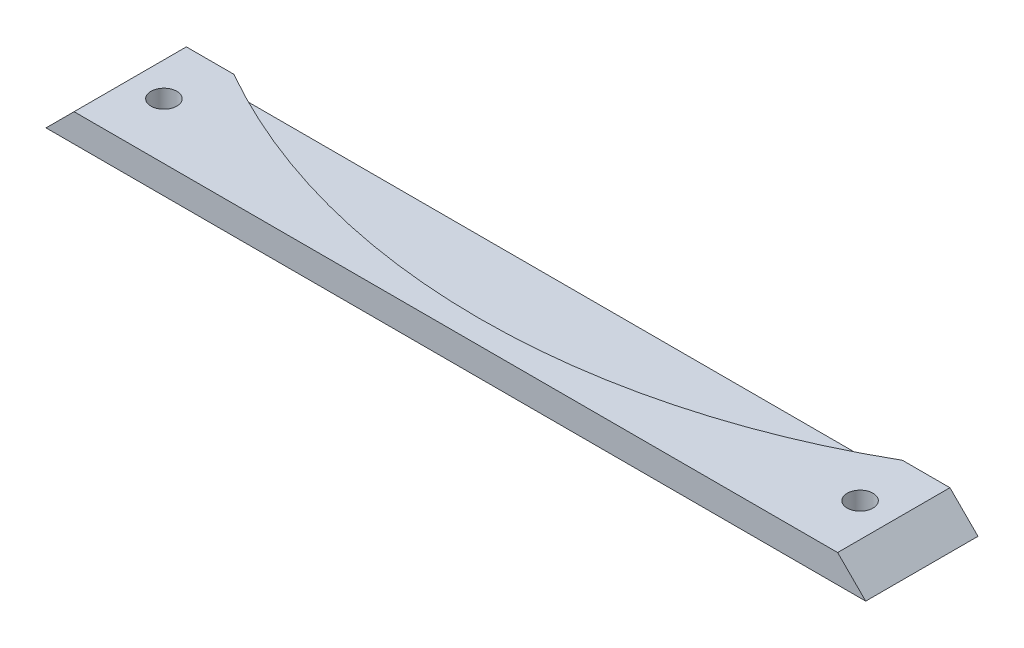
SolidWorks part; units mm, degrees
ref_plane "Front Plane" through (0, 0, 0) normal (0, 0, 1) x (1, 0, 0)
ref_plane "Top Plane" through (0, 0, 0) normal (0, 1, 0) x (1, 0, 0)
ref_plane "Right Plane" through (0, 0, 0) normal (1, 0, 0) x (0, 0, -1)
sketch "Sketch1" plane through (0, 0, 0) normal (0, 1, 0) x (1, 0, 0)
  line L1 (-75, -10) -> (75, -10)
  line L2 (-75, -10) -> (-75, 10)
  line L3 (-75, 10) -> (75, 10)
  line L4 (75, -10) -> (75, 10)
  line L5 (-75, -10) -> (75, 10) construction
  line L6 (-75, 10) -> (75, -10) construction
  point P0 (0, 0)
  dimension "D1" = 20
  dimension "D2" = 150
extrude "Boss-Extrude1" add sketch "Sketch1" along normal blind 5
sketch "Sketch2" plane through (0, 5, 0) normal (0, 1, 0) x (1, 0, 0)
  circle A0 centre (0, 114.3) radius 120.1
  dimension "D1" = 240.2
  dimension "D2" = 114.3
extrude "Cut-Extrude1" cut sketch "Sketch2" against normal blind 3
sketch "Sketch3" plane through (0, 0, 0) normal (0, 1, 0) x (1, 0, 0)
  line L0 (-75, 0) -> (75, 0) construction
  line L1 (-75, 10) -> (-75, -10) construction
  line L2 (75, -10) -> (75, 10) construction
  circle A0 centre (-62, 0) radius 2.3
  circle A1 centre (62, 0) radius 2.3
  dimension "D1" = 4.6
  dimension "D2" = 13
  dimension "D3" = 13
extrude "Cut-Extrude4" cut sketch "Sketch3" along normal through all
chamfer "Chamfer1" distance 7 angle 45 2 edges at (75, 5, 0) (-75, 5, 0)
